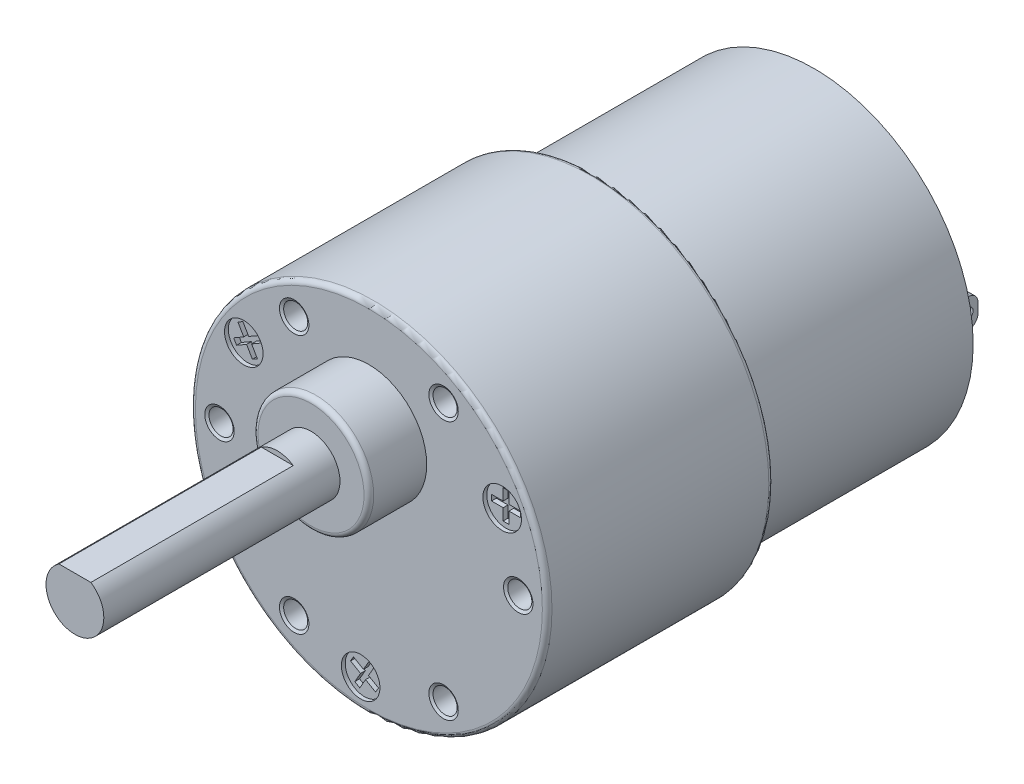
SolidWorks part; units mm, degrees
material "氧化铝"
ref_plane "前视基准面" through (0, 0, 0) normal (0, 0, 1) x (1, 0, 0)
ref_plane "上视基准面" through (0, 0, 0) normal (0, 1, 0) x (1, 0, 0)
ref_plane "右视基准面" through (0, 0, 0) normal (1, 0, 0) x (0, 0, -1)
sketch "草图1" plane through (0, 0, 0) normal (0, 0, 1) x (1, 0, 0)
  circle A0 centre (0, 0) radius 16.5
extrude "凸台-拉伸1" add sketch "草图1" along normal blind 22.7
sketch "草图2" plane through (0, 0, 22.7) normal (0, 0, 1) x (1, 0, 0)
  circle A0 centre (0, 0) radius 18.5
  dimension "D1" = 37
extrude "凸台-拉伸2" add sketch "草图2" along normal blind 23.5
sketch "草图3" plane through (0, 0, 46.2) normal (0, 0, 1) x (1, 0, 0)
  line L0 (0, 18.2228) -> (0, -18.5) construction
  circle A0 centre (0, 0) radius 18.5 construction
  circle A1 centre (0, 7) radius 6
  dimension "D1" = 7
extrude "凸台-拉伸3" add sketch "草图3" along normal blind 6
sketch "草图4" plane through (0, 0, 52.2) normal (0, 0, 1) x (1, 0, 0)
  circle A0 centre (0, 7) radius 3
extrude "凸台-拉伸4" add sketch "草图4" along normal blind 15.5
sketch "草图5" plane through (0, 0, 67.7) normal (0, 0, 1) x (1, 0, 0)
  line L0 (-1.6583, 9.5) -> (1.6583, 9.5)
  circle A0 centre (0, 7) radius 3 construction
  arc A1 (1.6583, 9.5) -> (-1.6583, 9.5) centre (0, 7) ccw
  dimension "D1" = 2.5
extrude "切除-拉伸1" cut sketch "草图5" against normal blind 12
sketch "草图6" plane through (0, 0, 0) normal (0, 0, -1) x (-1, 0, 0)
  line L0 (0, 18.5) -> (0, -18.5) construction
  line L1 (-18.5, 0) -> (18.5, 0) construction
  line L2 (-13.5, -1.5) -> (-12.5, -1.5)
  line L3 (-13.5, 1.5) -> (-12.5, 1.5)
  line L4 (-13.5, 1.5) -> (-13.5, -1.5)
  line L5 (12.5, 1.5) -> (12.5, -1.5)
  line L6 (-12.5, 1.5) -> (-12.5, -1.5)
  line L7 (13.5, 1.5) -> (13.5, -1.5)
  line L8 (13.5, 1.5) -> (12.5, 1.5)
  line L9 (13.5, -1.5) -> (12.5, -1.5)
  circle A1 centre (0, 0) radius 18.5 construction
  point P12 (-12.5, 0)
  point P16 (-13.5, 0)
  point P20 (13.5, 0)
  point P21 (12.5, 0)
  dimension "D1" = 1
  dimension "D2" = 1.5
  dimension "D3" = 5
extrude "凸台-拉伸5" add sketch "草图6" along normal blind 3.5
sketch "草图7" plane through (0, 0, 0) normal (0, 0, -1) x (-1, 0, 0)
  circle A0 centre (0, 0) radius 1.5
extrude "凸台-拉伸6" add sketch "草图7" along normal blind 1.5
sketch "草图8" plane through (13.5, 0, 0) normal (1, 0, 0) x (0, 0, -1)
  line L0 (3.5, 1.5) -> (3.5, -1.5) construction
  circle A0 centre (2.5, 0) radius 0.5
  point P2 (3.5, 0)
  dimension "D1" = 1
extrude "切除-拉伸2" cut sketch "草图8" against normal through all
fillet "圆角5" radius 1 4 edges at (-13, 1.5, -3.5) (-13, -1.5, -3.5) (13, 1.5, -3.5) (13, -1.5, -3.5)
hole_wizard "M3 螺纹孔3" positions "草图14" profile "草图13" tap size "M3" standard "Gb"
sketch "草图14" plane through (0, 0, 46.2) normal (0, 0, 1) x (1, 0, 0)
  line L0 (0, 0) -> (0, 18.5) construction
  line L3 (0, 0) -> (7.75, 13.4234) construction
  circle A0 centre (0, 0) radius 18.5 construction
  circle A1 centre (0, 0) radius 15.5 construction
  point P12 (7.75, 13.4234)
  dimension "D1" = 30
  dimension "D2" = 31
sketch "草图13" plane through (7.75, 13.4234, 46.2) normal (1, 0, 0) x (0, -1, 0)
  line L0 (0, 0) -> (0, 7.2511)
  line L1 (0, 7.2511) -> (1.25, 6.5)
  line L2 (1.25, 6.5) -> (1.25, 0.1588)
  line L3 (1.25, 0.1588) -> (1.525, 0)
  line L5 (1.525, 0) -> (0, 0)
  line L6 (-1.25, 0.1588) -> (-1.525, 0) construction
  line L10 (0, 7.2511) -> (-1.25, 6.5) construction
  line L11 (0, -6.35) -> (0, 107.95) construction
  dimension "螺纹孔钻头直径" = 2.5
  dimension "螺纹孔钻头深度" = 6.5
  dimension "近端锥形沉头孔直径" = 3.05
  dimension "近端锥形沉头孔角度" = 120
  dimension "导头角度" = 118
cosmetic thread "孔螺蚊线3" parameters "D1"=4, "D2"=3
ref_axis "基准轴1" through (0, 0, -7.35) along (0, 0, 1)
pattern_circular "阵列(圆周)1" count 6 over 360 about axis through (0, 0, -7.35) along (0, 0, 1) of "M3 螺纹孔3"
sketch "草图15" plane through (0, 0, 46.2) normal (0, 0, 1) x (1, 0, 0)
  circle A0 centre (13.8293, 7) radius 2
  circle A1 centre (0, 0) radius 15.5 construction
  dimension "D1" = 7
extrude "切除-拉伸3" cut sketch "草图15" against normal blind 0.4
sketch "草图17" plane through (0, 0, 45.8) normal (0, 0, 1) x (1, 0, 0)
  line L0 (13.8293, 9) -> (13.8293, 5) construction
  line L1 (11.8293, 7) -> (15.8293, 7) construction
  line L2 (13.5293, 5.5) -> (13.5293, 6.7)
  line L3 (13.5293, 8.5) -> (14.1293, 8.5)
  line L4 (14.1293, 5.5) -> (14.1293, 6.7)
  line L5 (13.8293, 7) -> (15.1633, 5.666) construction
  line L6 (12.3293, 7.3) -> (12.3293, 6.7)
  line L7 (15.3293, 6.7) -> (14.1293, 6.7)
  line L8 (15.3293, 7.3) -> (14.1293, 7.3)
  line L9 (13.5293, 6.7) -> (12.3293, 6.7)
  line L10 (13.5293, 7.3) -> (12.3293, 7.3)
  line L11 (13.5293, 5.5) -> (14.1293, 5.5)
  line L12 (15.3293, 7.3) -> (15.3293, 6.7)
  line L13 (13.5293, 7.3) -> (13.5293, 8.5)
  line L15 (14.1293, 7.3) -> (14.1293, 8.5)
  circle A0 centre (13.8293, 7) radius 2 construction
  circle A1 centre (13.8293, 7) radius 2 construction
  point P9 (13.8293, 5.5)
  point P13 (13.8293, 8.5)
  point P21 (14.1293, 7)
  point P22 (13.5293, 7)
  dimension "D1" = 0.3
  dimension "D2" = 1.5
extrude "切除-拉伸4" cut sketch "草图17" against normal blind 0.5
pattern_circular "阵列(圆周)2" count 3 over 360 about axis through (0, 0, -7.35) along (0, 0, 1) of "切除-拉伸3", "切除-拉伸4"
fillet "圆角6" radius 0.5 3 edges at (6, 7, 52.2) (18.5, 0, 46.2) (18.5, 0, 22.7)
sketch "草图18" plane through (0, 0, 0) normal (0, 0, -1) x (-1, 0, 0)
  circle A0 centre (0, 0) radius 16
extrude "切除-拉伸5" cut sketch "草图18" against normal blind 0.6
fillet "圆角7" radius 0.2 1 edges at (-1.5, 0, -1.5)
chamfer "倒角1" distance 0.3 angle 45 2 edges at (0, 9.5, 67.7) (0, 4, 67.7)
sketch "草图19" plane through (0, 0, 0) normal (1, 0, 0) x (0, 0, -1)
  line L0 (22.4957, 7) -> (-142.0758, 7)
sketch "草图20" plane through (0, 0, 46.2) normal (0, 0, 1) x (1, 0, 0)
  line L0 (0, 18.5) -> (0, -18.5)
  circle A0 centre (0, 0) radius 18.5 construction
sketch "Sketch1" plane through (0, 0, 67.7) normal (0, 0, 1) x (1, 0, 0)
  line L0 (-1.6583, 9.5) -> (1.6583, 9.5)
  line L1 (0, 9.2) -> (0, 4.3) construction
  line L2 (1.5652, 9.2) -> (-1.5652, 9.2) construction
  line L3 (-2.7, 7) -> (2.7, 7) construction
  arc A0 (-1.6583, 9.5) -> (1.6583, 9.5) centre (0, 7) ccw construction
  arc A1 (-1.5652, 9.2) -> (1.5652, 9.2) centre (0, 7) ccw construction
  arc A2 (1.6583, 9.5) -> (-1.6583, 9.5) centre (0, 7) cw
  spline S0 degree 3 poles (1.5652, 9.2) (1.5971, 9.2999) (1.6281, 9.3999) (1.6583, 9.5) knots 0 0 0 0 0.000434 0.000434 0.000434 0.000434 construction
  arc M1 (-1.5652, 9.2) -> (1.5652, 9.2) centre (0, 7) ccw
  line M2 (1.5652, 9.2) -> (-1.5652, 9.2)
extrude "Boss-Extrude1" add sketch "Sketch1" along normal blind 10 from offset 1 contours M2 M1 | A2 L0 M1 M2 region at (0, 9.4186, 67.7) region at (0, 6.8829, 67.7) offset against normal yes
